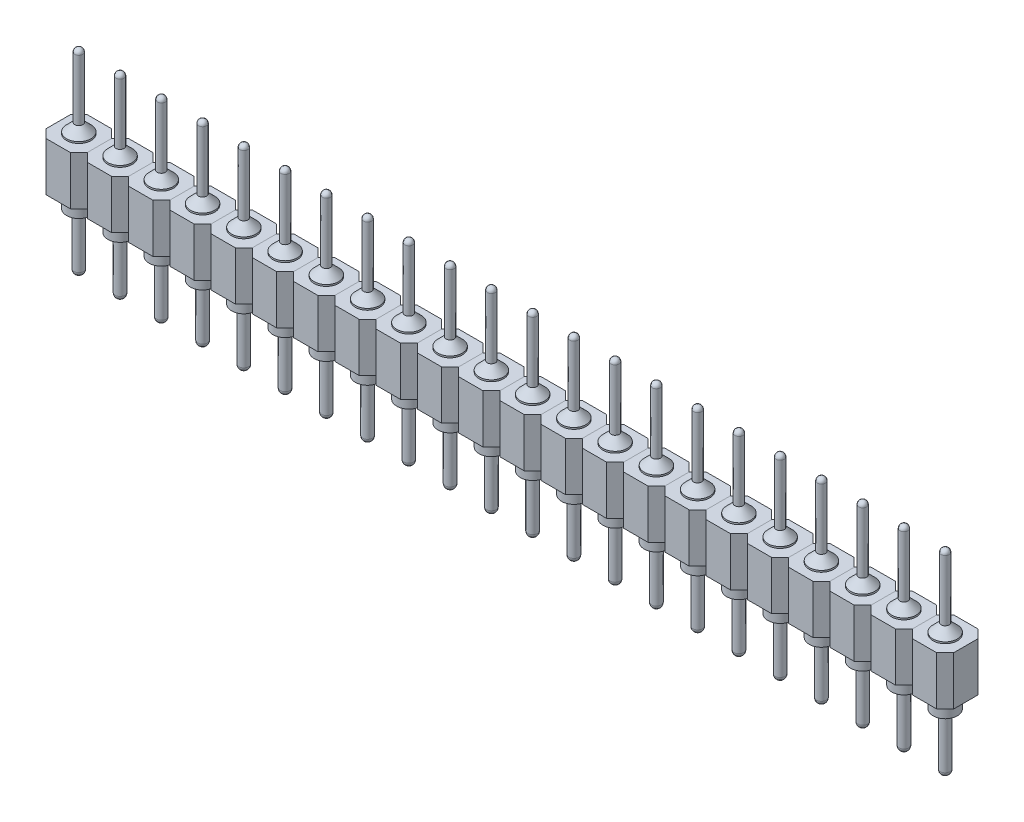
SolidWorks part; units mm, degrees
ref_plane "Спереди" through (0, 0, 0) normal (0, 0, 1) x (1, 0, 0)
ref_plane "Сверху" through (0, 0, 0) normal (0, 1, 0) x (1, 0, 0)
ref_plane "Справа" through (0, 0, 0) normal (1, 0, 0) x (0, 0, -1)
other "Configuration Table"
sketch "Эскиз2" plane through (0, 0, 0) normal (0, 0, 1) x (1, 0, 0)
  line L0 (0, 12.1) -> (0, 0) construction
  line L1 (0, 0) -> (0, 12.1)
  line L2 (0.3, 0.3) -> (0.3, 3.5)
  line L3 (0.3, 3.5) -> (0.75, 3.5)
  line L4 (0.75, 3.5) -> (0.75, 7.6)
  line L5 (0.25, 11.85) -> (0.25, 8.1)
  line L6 (0.25, 8.1) -> (0.75, 7.6)
  circle A0 centre (0, 11.85) radius 0.25
  circle A1 centre (0, 0.3) radius 0.3
  point P11 (0, 8.4658)
  point P14 (0.8933, 4.0058)
  point P15 (0.9619, 3.7451)
  dimension "D1" = 0.5
  dimension "D2" = 0.6
  dimension "D3" = 4
  dimension "D4" = 0.5
  dimension "D5" = 4.1
  dimension "D6" = 3.5
  dimension "D7" = 0.75
revolve "Повернуть1" add sketch "Эскиз2" angle 360 about L1 region at (0.1273, 0.3, 0) region at (0.2877, 5.7983, 0) region at (0.1061, 11.85, 0)
sketch "Эскиз3" plane through (0, 3.5, 0) normal (0, -1, 0) x (1, 0, 0)
  line L0 (0, 1.27) -> (0, -1.27) construction
  line L1 (-0.75, 1.27) -> (0.75, 1.27)
  line L2 (-1.27, 0.75) -> (-1.27, -0.75)
  line L3 (-0.75, -1.27) -> (0.75, -1.27)
  line L4 (1.27, 0.75) -> (1.27, -0.75)
  line L5 (-1.27, 0.75) -> (-0.75, 1.27)
  line L6 (0.75, 1.27) -> (1.27, 0.75)
  line L7 (0.75, -1.27) -> (1.27, -0.75)
  line L8 (-1.27, -0.75) -> (-0.75, -1.27)
  circle A0 centre (0, 0) radius 0.75
  point P0 (-1.27, 1.27)
  point P1 (1.27, -1.27)
  point P2 (-1.27, -1.27)
  point P3 (1.27, 1.27)
  point P9 (0, 0)
  point P18 (0.7917, 1.4168)
  point P19 (0, 0)
  point P20 (0, 0)
  point P21 (0, 0)
  dimension "D2" = 1.5
  dimension "D1" = 2.54
  dimension "D3" = 2.54
extrude "Бобышка-Вытянуть1" add sketch "Эскиз3" against normal blind 3 from offset 1 separate body offset against normal yes
pattern_linear "Линейный массив1" count 22 spacing 2.54 along (-1, 0, 0) of bodies 103 104
